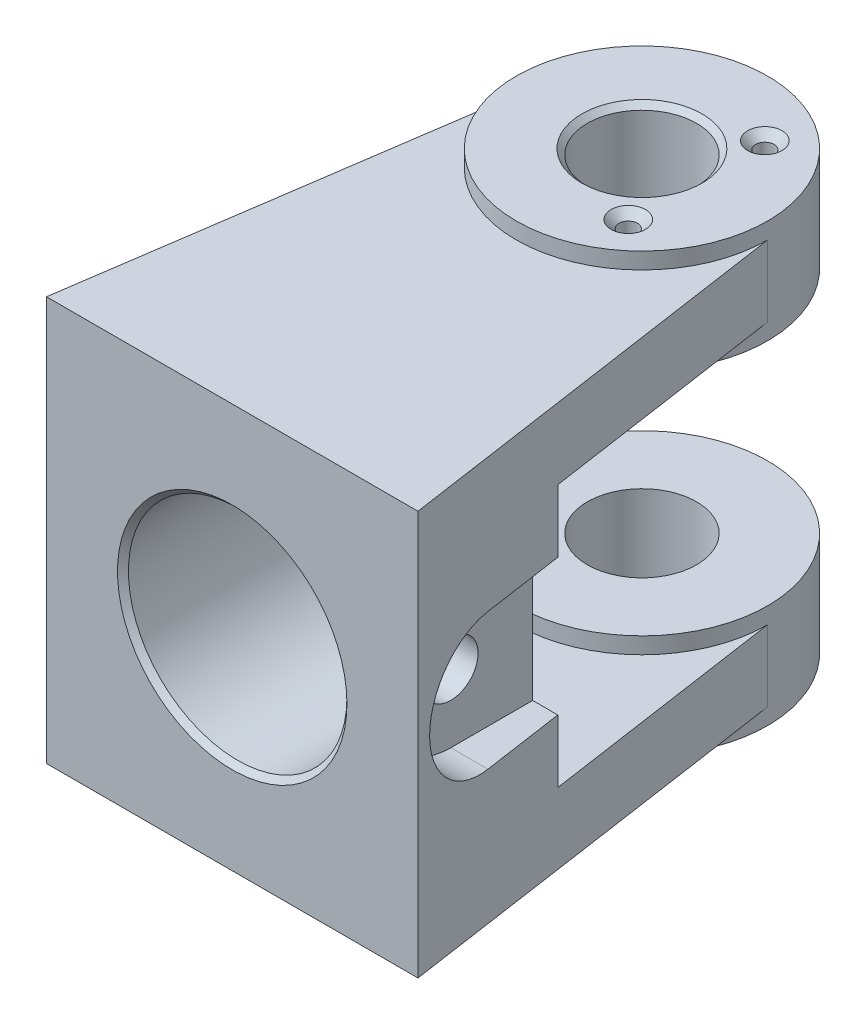
SolidWorks part; units mm, degrees
ref_plane "Front Plane" through (0, 0, 0) normal (0, 0, 1) x (1, 0, 0)
ref_plane "Top Plane" through (0, 0, 0) normal (0, 1, 0) x (1, 0, 0)
ref_plane "Right Plane" through (0, 0, 0) normal (1, 0, 0) x (0, 0, -1)
sketch "Sketch1" plane through (0, 0, 0) normal (0, 1, 0) x (1, 0, 0)
  line L0 (34, -75) -> (-34, -75)
  line L1 (-23, 0) -> (23, 0) construction
  line L2 (-23, 0) -> (-34, -75)
  line L3 (23, 0) -> (34, -75)
  arc A2 (-23, 0) -> (23, 0) centre (0, 0) ccw
  point P1 (0, -23)
  dimension "D1" = 23
  dimension "D2" = 68
  dimension "D3" = 75
extrude "Boss-Extrude2" add sketch "Sketch1" along normal mid plane 13 contours A2 L2 L0 L3 region at (0, 0, 47.1868)
sketch "Sketch2" plane through (0, 0, 0) normal (0, 1, 0) x (1, 0, 0)
  circle A0 centre (0, 0) radius 23
  circle A1 centre (0, 0) radius 10
  dimension "D1" = 20
  dimension "D2" = 46
extrude "Boss-Extrude3" add sketch "Sketch2" along normal mid plane 19
sketch "Sketch3" plane through (0, 6.5, 0) normal (0, 1, 0) x (1, 0, 0)
  line L0 (-29.6, -45) -> (29.6, -45)
  line L1 (-23, 0) -> (-34, -75) construction
  line L2 (23, 0) -> (34, -75) construction
  line L4 (34, -75) -> (-34, -75) construction
  line L8 (-23, 0) -> (-34, -75)
  line L9 (-34, -75) -> (34, -75)
  line L10 (34, -75) -> (23, 0)
  line L11 (-29.6, -45) -> (-34, -75)
  line L12 (-34, -75) -> (34, -75)
  line L13 (34, -75) -> (29.6, -45)
  arc A1 (-23, 0) -> (23, 0) centre (0, 0) ccw
  dimension "D1" = 30
  dimension "D2" = 0
extrude "Boss-Extrude4" add sketch "Sketch3" along normal blind 24
ref_plane "Plane1" through (0, 30.5, 0) normal (0, 1, 0) x (1, 0, 0)
chamfer "Chamfer2" distance 1 angle 45 1 edges at (0, -9.5, 10)
hole_wizard "CSK for M3 Countersunk Raised Head Screw2" positions "Sketch11" profile "Sketch12" countersink size "M3" standard "ISO"
sketch "Sketch11" plane through (0, -9.5, 0) normal (0, -1, 0) x (-1, 0, 0)
  line L0 (0, 23) -> (0, -23) construction
  line L2 (-23, 0) -> (23, 0) construction
  line L4 (-10, 12.5) -> (-10, -12.5) construction
  circle A0 centre (0, 0) radius 23 construction
  arc A1 (-23, 0) -> (23, 0) centre (0, 0) ccw construction
  point P0 (-10, 12.5)
  point P2 (-10, -12.5)
  point P23 (-10, 0)
  dimension "D1" = 10
  dimension "D2" = 25
sketch "Sketch12" plane through (10, -9.5, -12.5) normal (1, 0, 0) x (0, 0, -1)
  line L0 (0, 0) -> (0, 12)
  line L1 (0, 12) -> (1.7, 10.9785)
  line L2 (1.7, 10.9785) -> (1.7, 1.45)
  line L3 (1.7, 1.45) -> (3.15, 0)
  line L5 (3.15, 0) -> (0, 0)
  line L6 (-1.7, 1.45) -> (-3.15, 0) construction
  line L10 (0, 12) -> (-1.7, 10.9785) construction
  line L11 (0, -6.35) -> (0, 107.95) construction
  dimension "Диаметр отверстия" = 3.4
  dimension "Глубина отверстия" = 12
  dimension "Диаметр передней зенковки" = 6.3
  dimension "Угол передней зенковки" = 90
  dimension "Угол заточки сверла" = 118
mirror "Mirror4" about plane through (0, 30.5, 0) normal (0, 1, 0) of "CSK for M3 Countersunk Raised Head Screw2", "Boss-Extrude2", "Boss-Extrude3", "Boss-Extrude4", "Chamfer2"
sketch "Sketch4" plane through (0, 0, 75) normal (0, 0, 1) x (1, 0, 0)
  line L0 (-34, 30.5) -> (34, 30.5) construction
  line L1 (-34, 67.5) -> (-34, -6.5) construction
  line L2 (34, 67.5) -> (34, -6.5) construction
  line L3 (0, 67.5) -> (0, -6.5) construction
  line L4 (34, 67.5) -> (-34, 67.5) construction
  line L5 (34, -6.5) -> (-34, -6.5) construction
  circle A0 centre (0, 30.5) radius 20
  dimension "D1" = 40
extrude "Cut-Extrude1" cut sketch "Sketch4" against normal through all
ref_plane "Plane2" through (34, 0, 0) normal (1, 0, 0) x (0, 0, -1)
sketch "Sketch6" plane through (34, 0, 0) normal (1, 0, 0) x (0, 0, -1)
  line L0 (-45, 30.5) -> (-75, 30.5) construction
  line L1 (-60, 30.5) -> (-60, 18) construction
  line L2 (-60, 30.5) -> (-60, 43) construction
  line L3 (-60, 43) -> (-45, 43)
  line L4 (-60, 18) -> (-45, 18)
  line L5 (-45, 43) -> (-45, 18)
  line L8 (-75, -6.5) -> (0, -6.5)
  line L9 (0, -6.5) -> (0, 6.5)
  line L10 (0, 6.5) -> (-45, 6.5)
  line L11 (-45, 6.5) -> (-45, 54.5)
  line L12 (-45, 54.5) -> (0, 54.5)
  line L13 (0, 54.5) -> (0, 67.5)
  line L14 (0, 67.5) -> (-75, 67.5)
  line L15 (-75, 67.5) -> (-75, -6.5)
  line L16 (-75, -6.5) -> (0, -6.5) construction
  line L17 (0, -6.5) -> (0, 6.5) construction
  line L18 (0, 6.5) -> (-45, 6.5) construction
  line L19 (-45, 6.5) -> (-45, 54.5) construction
  line L20 (-45, 54.5) -> (0, 54.5) construction
  line L21 (0, 54.5) -> (0, 67.5) construction
  line L22 (0, 67.5) -> (-75, 67.5) construction
  line L23 (-75, 67.5) -> (-75, -6.5) construction
  arc A1 (-60, 18) -> (-60, 43) centre (-60, 30.5) cw
  circle A2 centre (-60, 30.5) radius 5
  dimension "D2" = 12.5
  dimension "D4" = 10
  dimension "D3" = 15
  dimension "D1" = 0
extrude "Cut-Extrude2" cut sketch "Sketch6" against normal blind 9 from surface contours L3 L5 L4 A1 starting at plane "Plane2"
extrude "Cut-Extrude3" cut sketch "Sketch6<5>" against normal up to next contours A2
sketch "Sketch6<5>" plane through (34, 0, 0) normal (1, 0, 0) x (0, 0, -1) same geometry as "Sketch6"
chamfer "Chamfer3" distance 1 angle 45 1 edges at (20, 30.5, 75)
